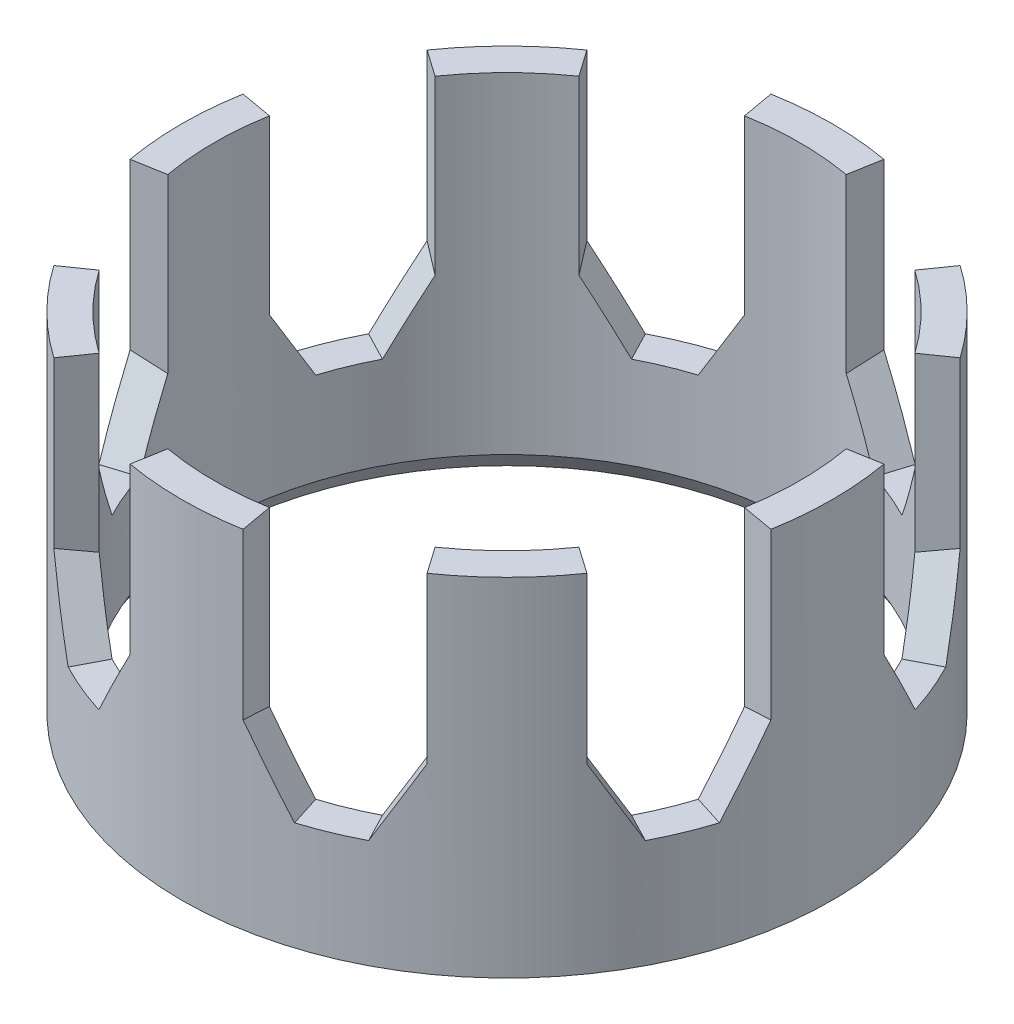
SolidWorks part; units mm, degrees
ref_plane "Front Plane" through (0, 0, 0) normal (0, 0, 1) x (1, 0, 0)
ref_plane "Top Plane" through (0, 0, 0) normal (0, 1, 0) x (1, 0, 0)
ref_plane "Right Plane" through (0, 0, 0) normal (1, 0, 0) x (0, 0, -1)
sketch "Sketch1" plane through (0, 0, 0) normal (0, 1, 0) x (1, 0, 0)
  circle A0 centre (0, 0) radius 27
  circle A1 centre (0, 0) radius 30
  dimension "D1" = 54
  dimension "D2" = 60
extrude "Boss-Extrude1" add sketch "Sketch1" along normal blind 10
sketch "Sketch2" plane through (0, 10, 0) normal (0, 1, 0) x (1, 0, 0)
  line L2 (0, 27) -> (0, 30) construction
  line L17 (8.1191, 25.7504) -> (9.0212, 28.6115)
  line L18 (-8.1191, 25.7504) -> (-9.0212, 28.6115)
  line L19 (12.4672, 23.9493) -> (13.8525, 26.6103)
  line L20 (23.9493, 12.4672) -> (26.6103, 13.8525)
  line L21 (25.7504, 8.1191) -> (28.6115, 9.0212)
  line L22 (25.7504, -8.1191) -> (28.6115, -9.0212)
  line L23 (23.9493, -12.4672) -> (26.6103, -13.8525)
  line L24 (12.4672, -23.9493) -> (13.8525, -26.6103)
  line L25 (8.1191, -25.7504) -> (9.0212, -28.6115)
  line L26 (-8.1191, -25.7504) -> (-9.0212, -28.6115)
  line L27 (-12.4672, -23.9493) -> (-13.8525, -26.6103)
  line L28 (-23.9493, -12.4672) -> (-26.6103, -13.8525)
  line L29 (-25.7504, -8.1191) -> (-28.6115, -9.0212)
  line L30 (-25.7504, 8.1191) -> (-28.6115, 9.0212)
  line L31 (-23.9493, 12.4672) -> (-26.6103, 13.8525)
  line L32 (-12.4672, 23.9493) -> (-13.8525, 26.6103)
  arc A0 (26.6103, 13.8525) -> (13.8525, 26.6103) centre (0, 0) ccw
  arc A1 (23.9493, 12.4672) -> (12.4672, 23.9493) centre (0, 0) ccw
  circle A18 centre (0, 0) radius 30 construction
  circle A19 centre (0, 0) radius 27 construction
  arc A20 (8.1191, 25.7504) -> (-8.1191, 25.7504) centre (0, 0) ccw
  arc A21 (9.0212, 28.6115) -> (-9.0212, 28.6115) centre (0, 0) ccw
  arc A22 (28.6115, -9.0212) -> (28.6115, 9.0212) centre (0, 0) ccw
  arc A23 (25.7504, -8.1191) -> (25.7504, 8.1191) centre (0, 0) ccw
  arc A24 (13.8525, -26.6103) -> (26.6103, -13.8525) centre (0, 0) ccw
  arc A25 (12.4672, -23.9493) -> (23.9493, -12.4672) centre (0, 0) ccw
  arc A26 (-9.0212, -28.6115) -> (9.0212, -28.6115) centre (0, 0) ccw
  arc A27 (-8.1191, -25.7504) -> (8.1191, -25.7504) centre (0, 0) ccw
  arc A28 (-26.6103, -13.8525) -> (-13.8525, -26.6103) centre (0, 0) ccw
  arc A29 (-23.9493, -12.4672) -> (-12.4672, -23.9493) centre (0, 0) ccw
  arc A30 (-28.6115, 9.0212) -> (-28.6115, -9.0212) centre (0, 0) ccw
  arc A31 (-25.7504, 8.1191) -> (-25.7504, -8.1191) centre (0, 0) ccw
  arc A32 (-13.8525, 26.6103) -> (-26.6103, 13.8525) centre (0, 0) ccw
  arc A33 (-12.4672, 23.9493) -> (-23.9493, 12.4672) centre (0, 0) ccw
  dimension "D1" = 35
  dimension "D2" = 17.5
  dimension "D3" = 8
  dimension "D4" = 3
  dimension "D5" = 3
extrude "Boss-Extrude2" add sketch "Sketch2" along normal blind 7
sketch "Sketch3" plane through (0, 17, 0) normal (0, 1, 0) x (1, 0, 0)
  line L0 (0, 27) -> (0, 30) construction
  line L1 (4.6885, 26.5898) -> (5.2094, 29.5442)
  line L2 (-4.6885, 26.5898) -> (-5.2094, 29.5442)
  line L3 (15.4866, 22.1171) -> (17.2073, 24.5746)
  line L4 (22.1171, 15.4866) -> (24.5746, 17.2073)
  line L5 (26.5898, 4.6885) -> (29.5442, 5.2094)
  line L6 (26.5898, -4.6885) -> (29.5442, -5.2094)
  line L7 (22.1171, -15.4866) -> (24.5746, -17.2073)
  line L8 (15.4866, -22.1171) -> (17.2073, -24.5746)
  line L9 (4.6885, -26.5898) -> (5.2094, -29.5442)
  line L10 (-4.6885, -26.5898) -> (-5.2094, -29.5442)
  line L11 (-15.4866, -22.1171) -> (-17.2073, -24.5746)
  line L12 (-22.1171, -15.4866) -> (-24.5746, -17.2073)
  line L13 (-26.5898, -4.6885) -> (-29.5442, -5.2094)
  line L14 (-26.5898, 4.6885) -> (-29.5442, 5.2094)
  line L15 (-22.1171, 15.4866) -> (-24.5746, 17.2073)
  line L16 (-15.4866, 22.1171) -> (-17.2073, 24.5746)
  arc A0 (9.0212, 28.6115) -> (-9.0212, 28.6115) centre (0, 0) ccw construction
  arc A1 (8.1191, 25.7504) -> (-8.1191, 25.7504) centre (0, 0) ccw construction
  arc A2 (4.6885, 26.5898) -> (-4.6885, 26.5898) centre (0, 0) ccw
  arc A3 (5.2094, 29.5442) -> (-5.2094, 29.5442) centre (0, 0) ccw
  arc A4 (24.5746, 17.2073) -> (17.2073, 24.5746) centre (0, 0) ccw
  arc A5 (22.1171, 15.4866) -> (15.4866, 22.1171) centre (0, 0) ccw
  arc A6 (29.5442, -5.2094) -> (29.5442, 5.2094) centre (0, 0) ccw
  arc A7 (26.5898, -4.6885) -> (26.5898, 4.6885) centre (0, 0) ccw
  arc A8 (17.2073, -24.5746) -> (24.5746, -17.2073) centre (0, 0) ccw
  arc A9 (15.4866, -22.1171) -> (22.1171, -15.4866) centre (0, 0) ccw
  arc A10 (-5.2094, -29.5442) -> (5.2094, -29.5442) centre (0, 0) ccw
  arc A11 (-4.6885, -26.5898) -> (4.6885, -26.5898) centre (0, 0) ccw
  arc A12 (-24.5746, -17.2073) -> (-17.2073, -24.5746) centre (0, 0) ccw
  arc A13 (-22.1171, -15.4866) -> (-15.4866, -22.1171) centre (0, 0) ccw
  arc A14 (-29.5442, 5.2094) -> (-29.5442, -5.2094) centre (0, 0) ccw
  arc A15 (-26.5898, 4.6885) -> (-26.5898, -4.6885) centre (0, 0) ccw
  arc A16 (-17.2073, 24.5746) -> (-24.5746, 17.2073) centre (0, 0) ccw
  arc A17 (-15.4866, 22.1171) -> (-22.1171, 15.4866) centre (0, 0) ccw
  dimension "D1" = 20
  dimension "D2" = 10
  dimension "D3" = 3
  dimension "D4" = 3
  dimension "D5" = 8
extrude "Boss-Extrude3" add sketch "Sketch3" along normal blind 15
chamfer "Chamfer1" distance 1.5 angle 30 1 edges at (0, 0, 27) first distance on face at (0, 19, 0)
chamfer "Chamfer3" distance 7 angle 30 1 edges at (8.5701, 17, -27.1809) first distance on face at (8.5701, 13.5, -27.1809)
chamfer "Chamfer4" distance 7 angle 30 1 edges at (13.1598, 17, -25.2798) first distance on face at (13.1598, 13.5, -25.2798)
chamfer "Chamfer5" distance 7 angle 30 1 edges at (25.2798, 17, -13.1598) first distance on face at (25.2798, 13.5, -13.1598)
chamfer "Chamfer6" distance 7 angle 30 1 edges at (27.1809, 17, -8.5701) first distance on face at (27.1809, 13.5, -8.5701)
chamfer "Chamfer7" distance 7 angle 30 2 edges at (25.2798, 17, 13.1598) (27.1809, 17, 8.5701) first distance on face at (25.2798, 13.5, 13.1598) first distance on face at (27.1809, 13.5, 8.5701)
chamfer "Chamfer8" distance 7 angle 30 2 edges at (8.5701, 17, 27.1809) (13.1598, 17, 25.2798) first distance on face at (8.5701, 13.5, 27.1809) first distance on face at (13.1598, 13.5, 25.2798)
chamfer "Chamfer9" distance 7 angle 30 2 edges at (-13.1598, 17, 25.2798) (-8.5701, 17, 27.1809) first distance on face at (-13.1598, 13.5, 25.2798) first distance on face at (-8.5701, 13.5, 27.1809)
chamfer "Chamfer10" distance 7 angle 30 2 edges at (-27.1809, 17, 8.5701) (-25.2798, 17, 13.1598) first distance on face at (-27.1809, 13.5, 8.5701) first distance on face at (-25.2798, 13.5, 13.1598)
chamfer "Chamfer11" distance 7 angle 30 2 edges at (-27.1809, 17, -8.5701) (-25.2798, 17, -13.1598) first distance on face at (-27.1809, 13.5, -8.5701) first distance on face at (-25.2798, 13.5, -13.1598)
chamfer "Chamfer12" distance 7 angle 30 1 edges at (-8.5701, 17, -27.1809) first distance on face at (-8.5701, 13.5, -27.1809)
chamfer "Chamfer13" distance 7 angle 30 1 edges at (-13.1598, 17, -25.2798) first distance on face at (-13.1598, 13.5, -25.2798)
